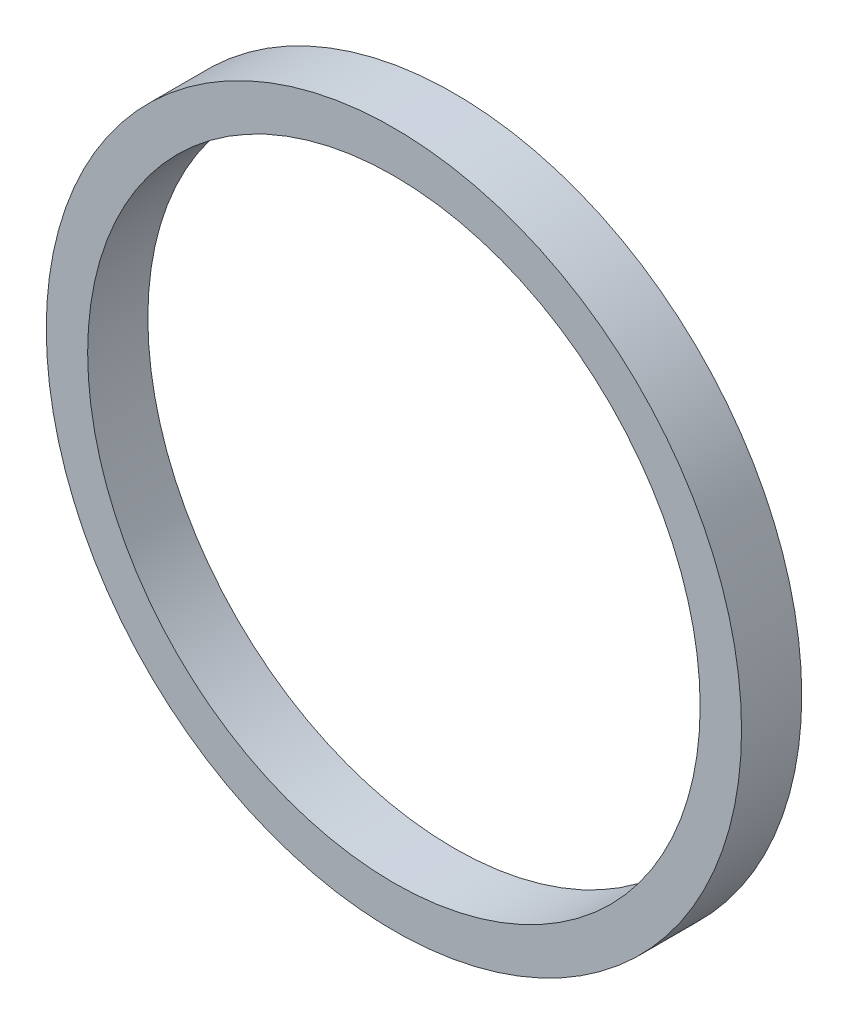
SolidWorks part; units mm, degrees
ref_plane "Front Plane" through (0, 0, 0) normal (0, 0, 1) x (1, 0, 0)
ref_plane "Top Plane" through (0, 0, 0) normal (0, 1, 0) x (1, 0, 0)
ref_plane "Right Plane" through (0, 0, 0) normal (1, 0, 0) x (0, 0, -1)
sketch "Sketch1" plane through (0, 0, 0) normal (0, 0, 1) x (1, 0, 0)
  circle A0 centre (0, 0) radius 5.0875
  circle A1 centre (0, 0) radius 5.775
  dimension "D1" = 10.175
  dimension "D2" = 11.55
extrude "Boss-Extrude1" add sketch "Sketch1" along normal blind 1
equation "\"RingPinShaft\"= 5"
equation "\"CenterBearingOut\"=32.05"
equation "\"RingPostIn\"=5.1"
equation "\"CamBearingOut\"=15.1"
equation "\"DiskOutputShaft\"=10.1"
equation "\"CenterShaft\"=25.2"
equation "\"Eccentricity\"=2"
equation "\"CycCamShaft\"=10.05"
equation "\"D1@Sketch1\"=\"CycCamShaft\" + 0.125"
equation "\"D2@Sketch1\"=\"CycCamShaft\"+1.5"
